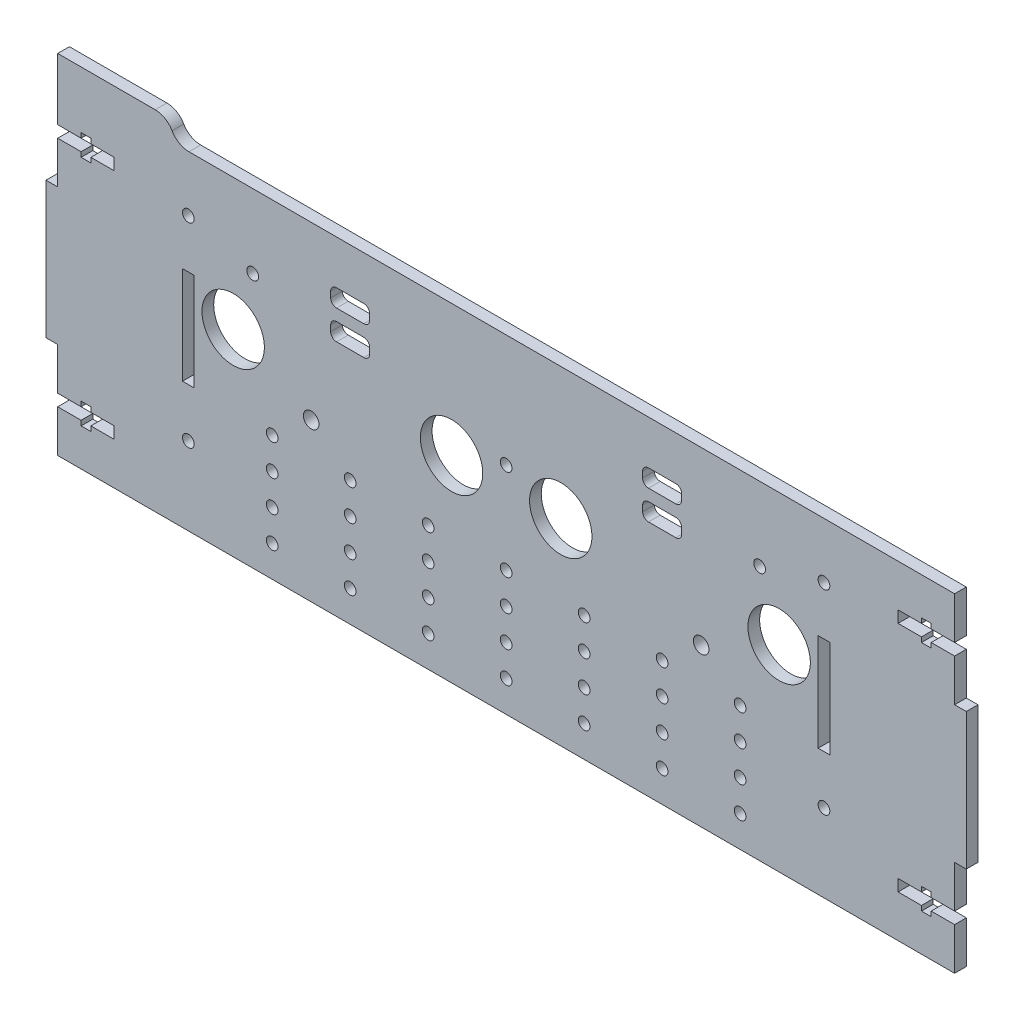
SolidWorks part; units mm, degrees
ref_plane "Спереди" through (0, 0, 0) normal (0, 0, 1) x (1, 0, 0)
ref_plane "Сверху" through (0, 0, 0) normal (0, 1, 0) x (1, 0, 0)
ref_plane "Справа" through (0, 0, 0) normal (1, 0, 0) x (0, 0, -1)
sketch "Эскиз1" plane through (0, 0, 0) normal (0, 0, 1) x (1, 0, 0)
  line L1 (0, 0) -> (230, 0)
  line L2 (0, 0) -> (0, 84.29)
  line L3 (0, 84.29) -> (230, 84.29)
  line L4 (230, 0) -> (230, 84.29)
  dimension "D1" = 84.29
  dimension "D2" = 230
extrude "Бобышка-Вытянуть1" add sketch "Эскиз1" along normal blind 3
sketch "Эскиз3" plane through (230, 0, 0) normal (1, 0, 0) x (0, 0, -1)
  line L0 (-3, 0) -> (-3, 84.29) construction
  line L1 (-3, 24.645) -> (0, 24.645)
  line L2 (-3, 24.645) -> (-3, 59.645)
  line L3 (-3, 59.645) -> (0, 59.645)
  line L4 (0, 24.645) -> (0, 59.645)
  line L5 (0, 0) -> (0, 84.29) construction
  point P9 (0, 42.145)
  point P10 (0, 42.145)
  dimension "D1" = 35
extrude "Бобышка-Вытянуть2" add sketch "Эскиз3" along normal blind 3 and the other way blind 233
sketch "Эскиз2" plane through (0, 0, 3) normal (0, 0, 1) x (1, 0, 0)
  line L0 (0, 0) -> (230, 0) construction
  circle A0 centre (65, 40.4) radius 2
  circle A1 centre (165, 40.4) radius 2
  point P8 (115, 0)
  dimension "D1" = 4
  dimension "D2" = 100
  dimension "D3" = 50
  dimension "D4" = 40.4
extrude "Вырез-Вытянуть1" cut sketch "Эскиз2" against normal blind 3
sketch "Эскиз5" plane through (0, 0, 3) normal (0, 0, 1) x (1, 0, 0)
  line L0 (0, 0) -> (230, 0) construction
  circle A0 centre (33.5, 70) radius 1.5
  circle A1 centre (33.5, 20) radius 1.5
  circle A2 centre (196.5, 20) radius 1.5
  circle A3 centre (196.5, 70) radius 1.5
  point P13 (115, 0)
  dimension "D1" = 3
  dimension "D2" = 20
  dimension "D3" = 163
  dimension "D4" = 81.5
  dimension "D5" = 50
extrude "Вырез-Вытянуть2" cut sketch "Эскиз5" against normal blind 3
sketch "Эскиз6" plane through (0, 0, 3) normal (0, 0, 1) x (1, 0, 0)
  line L0 (0, 0) -> (230, 0) construction
  line L1 (32, 32.5) -> (35, 32.5)
  line L2 (32, 32.5) -> (32, 57.5)
  line L3 (32, 57.5) -> (35, 57.5)
  line L4 (35, 32.5) -> (35, 57.5)
  line L5 (32, 32.5) -> (35, 57.5) construction
  line L6 (32, 57.5) -> (35, 32.5) construction
  line L7 (195, 32.5) -> (198, 32.5)
  line L8 (195, 32.5) -> (195, 57.5)
  line L9 (195, 57.5) -> (198, 57.5)
  line L10 (198, 32.5) -> (198, 57.5)
  line L11 (195, 32.5) -> (198, 57.5) construction
  line L12 (195, 57.5) -> (198, 32.5) construction
  circle A0 centre (33.5, 20) radius 1.5 construction
  point P0 (33.5, 45)
  point P5 (196.5, 45)
  point P16 (115, 0)
  dimension "D1" = 3
  dimension "D2" = 25
  dimension "D3" = 163
  dimension "D4" = 25
  dimension "D5" = 81.5
extrude "Вырез-Вытянуть3" cut sketch "Эскиз6" against normal blind 3
sketch "Эскиз7" plane through (0, 0, 3) normal (0, 0, 1) x (1, 0, 0)
  line L0 (0, 73.4675) -> (6, 73.4675)
  line L1 (6, 73.4675) -> (6, 74.7175)
  line L2 (6, 74.7175) -> (8.5, 74.7175)
  line L3 (8.5, 74.7175) -> (8.5, 73.4675)
  line L4 (8.5, 73.4675) -> (14.5, 73.4675)
  line L5 (14.5, 73.4675) -> (14.5, 70.4675)
  line L6 (14.5, 70.4675) -> (8.5, 70.4675)
  line L7 (8.5, 70.4675) -> (8.5, 69.2175)
  line L8 (8.5, 69.2175) -> (6, 69.2175)
  line L9 (6, 69.2175) -> (6, 70.4675)
  line L10 (6, 70.4675) -> (0, 70.4675)
  line L11 (0, 70.4675) -> (0, 73.4675)
  line L12 (0, 84.29) -> (0, 59.645) construction
  line L13 (-3, 42.145) -> (5.379, 42.145) construction
  line L14 (-3, 59.645) -> (-3, 24.645) construction
  line L15 (115, 84.29) -> (115, 45.3561) construction
  line L16 (230, 84.29) -> (0, 84.29) construction
  line L17 (0, 13.8225) -> (0, 10.8225)
  line L18 (6, 13.8225) -> (0, 13.8225)
  line L19 (6, 15.0725) -> (6, 13.8225)
  line L20 (8.5, 15.0725) -> (6, 15.0725)
  line L21 (8.5, 13.8225) -> (8.5, 15.0725)
  line L22 (14.5, 13.8225) -> (8.5, 13.8225)
  line L23 (14.5, 10.8225) -> (14.5, 13.8225)
  line L24 (8.5, 10.8225) -> (14.5, 10.8225)
  line L25 (8.5, 9.5725) -> (8.5, 10.8225)
  line L26 (6, 9.5725) -> (8.5, 9.5725)
  line L27 (6, 10.8225) -> (6, 9.5725)
  line L28 (0, 10.8225) -> (6, 10.8225)
  line L29 (230, 10.8225) -> (224, 10.8225)
  line L30 (224, 10.8225) -> (224, 9.5725)
  line L31 (224, 9.5725) -> (221.5, 9.5725)
  line L32 (221.5, 9.5725) -> (221.5, 10.8225)
  line L33 (221.5, 10.8225) -> (215.5, 10.8225)
  line L34 (215.5, 10.8225) -> (215.5, 13.8225)
  line L35 (215.5, 13.8225) -> (221.5, 13.8225)
  line L36 (221.5, 13.8225) -> (221.5, 15.0725)
  line L37 (221.5, 15.0725) -> (224, 15.0725)
  line L38 (224, 15.0725) -> (224, 13.8225)
  line L39 (224, 13.8225) -> (230, 13.8225)
  line L40 (230, 13.8225) -> (230, 10.8225)
  line L41 (230, 70.4675) -> (230, 73.4675)
  line L42 (224, 70.4675) -> (230, 70.4675)
  line L43 (224, 69.2175) -> (224, 70.4675)
  line L44 (221.5, 69.2175) -> (224, 69.2175)
  line L45 (221.5, 70.4675) -> (221.5, 69.2175)
  line L46 (215.5, 70.4675) -> (221.5, 70.4675)
  line L47 (215.5, 73.4675) -> (215.5, 70.4675)
  line L48 (221.5, 73.4675) -> (215.5, 73.4675)
  line L49 (221.5, 74.7175) -> (221.5, 73.4675)
  line L50 (224, 74.7175) -> (221.5, 74.7175)
  line L51 (224, 73.4675) -> (224, 74.7175)
  line L52 (230, 73.4675) -> (224, 73.4675)
  point P16 (0, 71.9675)
  point P17 (0, 71.9675)
  dimension "D1" = 6
  dimension "D2" = 3
  dimension "D3" = 5.5
  dimension "D4" = 2.5
  dimension "D5" = 12.3225
extrude "Вырез-Вытянуть4" cut sketch "Эскиз7" against normal blind 3
sketch "Эскиз8" plane through (0, 84.29, 0) normal (0, 1, 0) x (1, 0, 0)
  line L0 (230, 0) -> (0, 0) construction
  line L1 (0, -3) -> (30, -3)
  line L2 (0, -3) -> (0, 0)
  line L3 (0, 0) -> (30, 0)
  line L4 (30, -3) -> (30, 0)
  dimension "D1" = 30
extrude "Бобышка-Вытянуть3" add sketch "Эскиз8" along normal blind 5
fillet "Скругление1" radius 5 1 edges at (30, 89.29, 1.5)
fillet "Скругление2" radius 5 1 edges at (30, 84.29, 1.5)
sketch "Эскиз9" plane through (0, 0, 0) normal (0, 0, -1) x (-1, 0, 0)
  line L0 (0, 0) -> (-230, 0) construction
  circle A0 centre (-180, 65.4) radius 1.5
  circle A1 centre (-50, 65.4) radius 1.5
  circle A4 centre (-115, 55.4) radius 1.5
  circle A5 centre (-165, 40.4) radius 2 construction
  point P8 (-115, 0)
  dimension "D1" = 3
  dimension "D2" = 130
  dimension "D3" = 65
  dimension "D5" = 15
  dimension "D4" = 10
extrude "Вырез-Вытянуть5" cut sketch "Эскиз9" against normal blind 10
sketch "Эскиз10" plane through (0, 0, 0) normal (0, 0, -1) x (-1, 0, 0)
  circle A0 centre (-185, 50.5) radius 8
  circle A1 centre (-129, 50.5) radius 8
  circle A2 centre (-101, 50.5) radius 8
  circle A3 centre (-45, 50.5) radius 8
  circle A4 centre (-115, 55.4) radius 1.5 construction
  dimension "D1" = 16
  dimension "D5" = 14
  dimension "D6" = 4.9
  dimension "D2" = 56
  dimension "D3" = 56
  dimension "D4" = 28
extrude "Вырез-Вытянуть6" cut sketch "Эскиз10" against normal blind 10
sketch "Эскиз11" plane through (0, 0, 0) normal (0, 0, -1) x (-1, 0, 0)
  line L0 (-160, 68.5) -> (-160, 65.5) construction
  line L1 (-160, 65.5) -> (-150, 65.5)
  line L2 (-160, 65.5) -> (-160, 61)
  line L3 (-160, 61) -> (-150, 61)
  line L4 (-150, 65.5) -> (-150, 61)
  line L5 (-80, 65.5) -> (-70, 65.5)
  line L6 (-80, 65.5) -> (-80, 61)
  line L7 (-80, 61) -> (-70, 61)
  line L8 (-70, 65.5) -> (-70, 61)
  line L9 (-70, 68.5) -> (-80, 68.5)
  line L10 (-70, 68.5) -> (-70, 73)
  line L11 (-70, 73) -> (-80, 73)
  line L12 (-80, 68.5) -> (-80, 73)
  line L13 (-150, 68.5) -> (-160, 68.5)
  line L14 (-150, 68.5) -> (-150, 73)
  line L15 (-150, 73) -> (-160, 73)
  line L16 (-160, 68.5) -> (-160, 73)
  circle A1 centre (-185, 50.5) radius 8 construction
  circle A3 centre (-115, 55.4) radius 1.5 construction
  point P8 (-155, 65.5)
  point P9 (-75, 65.5)
  point P10 (-75, 61)
  point P24 (-160, 67)
  dimension "D5" = 16.5
  dimension "D1" = 10
  dimension "D2" = 4.5
  dimension "D3" = 80
  dimension "D4" = 40
  dimension "D6" = 3
extrude "Вырез-Вытянуть7" cut sketch "Эскиз11" against normal blind 10
fillet "Скругление3" radius 1.5 16 edges at (80, 65.5, 1.5) (70, 65.5, 1.5) (150, 65.5, 1.5) (160, 65.5, 1.5) (160, 61, 1.5) (80, 61, 1.5) (150, 61, 1.5) (70, 61, 1.5) (70, 68.5, 1.5) (80, 68.5, 1.5) (70, 73, 1.5) (80, 73, 1.5) (160, 73, 1.5) (150, 73, 1.5) (150, 68.5, 1.5) (160, 68.5, 1.5)
sketch "Эскиз12" plane through (0, 0, 3) normal (0, 0, 1) x (1, 0, 0)
  line L0 (0, 0) -> (230, 0) construction
  line L1 (35, 32.5) -> (35, 57.5) construction
  circle A0 centre (55, 8) radius 1.5
  dimension "D1" = 3
  dimension "D2" = 8
  dimension "D3" = 20
extrude "Вырез-Вытянуть8" cut sketch "Эскиз12" against normal blind 10 contours A0
pattern_linear "Линейный массив1" count 7 spacing 20 along (1, 0, 0) count 4 spacing 8 along (0, 1, 0) of "Вырез-Вытянуть8"
